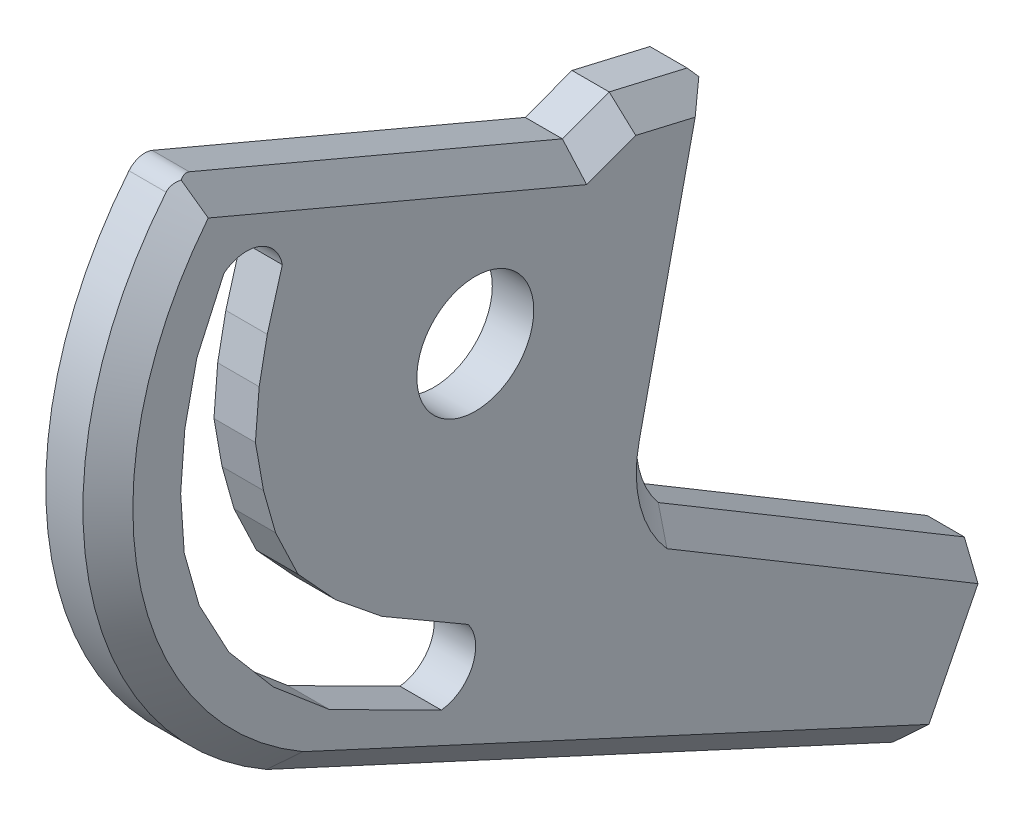
SolidWorks part; units mm, degrees
ref_plane "Front Plane" through (0, 0, 0) normal (0, 0, 1) x (1, 0, 0)
ref_plane "Top Plane" through (0, 0, 0) normal (0, 1, 0) x (1, 0, 0)
ref_plane "Right Plane" through (0, 0, 0) normal (1, 0, 0) x (0, 0, -1)
sketch "Sketch1" plane through (0, 0, 0) normal (1, 0, 0) x (0, 0, -1)
  line L0 (-32.2773, 373.0147) -> (-176.4769, 434.088)
  line L1 (-32.2773, 373.0147) -> (-14.1923, 379.6838)
  line L2 (-14.1923, 379.6838) -> (15.937, 372.6279)
  line L3 (15.937, 372.6279) -> (20.004, 367.4463)
  line L4 (4.7876, 232.7412) -> (123.0757, 162.0886)
  line L5 (123.0757, 162.0886) -> (95.4308, 107.1979)
  line L6 (95.4308, 107.1979) -> (-146.6474, 219.1027)
  line L7 (20.004, 367.4463) -> (-2.8283, 264.4678)
  arc A0 (-176.4769, 434.088) -> (-185.4304, 431.7266) centre (-179.3195, 426.7114) ccw
  arc A1 (-2.8283, 264.4678) -> (4.7876, 232.7412) centre (33.5047, 256.4121) ccw
  arc A2 (-185.4304, 431.7266) -> (-146.6474, 219.1027) centre (-75.9203, 341.8524) ccw
  point P15 (-206.502, 286.9138)
extrude "Boss-Extrude1" add sketch "Sketch1" along normal blind 16.0292
sketch "Sketch3" plane through (0, 0, 0) normal (1, 0, 0) x (0, 0, -1)
  line L8 (-78.2919, 238.2959) -> (-111.6505, 257.6792)
  line L9 (-111.6505, 257.6792) -> (-129.5034, 272.1379)
  line L10 (-129.5034, 272.1379) -> (-144.0934, 288.0154)
  line L11 (-144.0934, 288.0154) -> (-152.7635, 306.2173)
  line L12 (-150.1534, 394.6406) -> (-155.9692, 374.2553)
  line L13 (-155.9692, 374.2553) -> (-159.1107, 358.284)
  line L14 (-159.1107, 358.284) -> (-160.5603, 340.3603)
  line L15 (-160.5603, 340.3603) -> (-157.418, 322.6664)
  line L16 (-157.418, 322.6664) -> (-152.7635, 306.2173)
  line L17 (-88.7059, 214.8383) -> (-131.9141, 236.614)
  line L18 (-131.9141, 236.614) -> (-153.6977, 255.111)
  line L19 (-153.6977, 255.111) -> (-170.8186, 275.2926)
  line L20 (-170.8186, 275.2926) -> (-182.3268, 296.7429)
  line L21 (-182.3268, 296.7429) -> (-188.0723, 317.0301)
  line L22 (-188.0723, 317.0301) -> (-189.453, 337.7014)
  line L23 (-189.453, 337.7014) -> (-187.8531, 358.4545)
  line L24 (-187.8531, 358.4545) -> (-183.2089, 379.9098)
  line L25 (-183.2089, 379.9098) -> (-172.7454, 403.0434)
  arc A5 (-172.7454, 403.0434) -> (-150.1534, 394.6406) centre (-163.998, 391.9896) cw
  arc A6 (-78.2919, 238.2959) -> (-88.7059, 214.8383) centre (-90.2379, 229.5589) cw
  circle A7 centre (-75.5764, 330.8703) radius 22.5958
  circle A8 centre (-75.5764, 330.8703) radius 95.2308 construction
  circle A9 centre (-142.8532, 263.4704) radius 13.3731 construction
  point P17 (-144.0934, 288.0154)
  point P20 (-129.5034, 272.1379)
  point P24 (-182.3268, 296.7429)
  point P25 (-152.7635, 306.2173)
  point P28 (-142.8532, 263.4704)
  point P32 (-111.6505, 257.6792)
  point P35 (-157.418, 322.6664)
  point P38 (-160.5603, 340.3603)
  point P39 (-159.1107, 358.284)
  point P40 (-155.9692, 374.2553)
  point P43 (-158.9644, 405.1564)
  point P46 (-183.2089, 379.9098)
  point P47 (-187.8531, 358.4545)
  point P48 (-189.453, 337.7014)
  point P49 (-188.0723, 317.0301)
  point P50 (-170.8186, 275.2926)
  point P51 (-153.6977, 255.111)
  point P52 (-131.9141, 236.614)
  point P55 (-76.4347, 224.219)
  dimension "D39" = 45.1917
  dimension "D42" = 26.7462
extrude "Cut-Extrude1" cut sketch "Sketch3" along normal through all
sketch "Sketch4" plane through (0, 0, 0) normal (1, 0, 0) x (0, 0, -1)
  line L0 (-32.2773, 373.0147) -> (-176.4769, 434.088)
  line L1 (-32.2773, 373.0147) -> (-14.1923, 379.6838)
  line L2 (-14.1923, 379.6838) -> (15.937, 372.6279)
  line L3 (15.937, 372.6279) -> (20.004, 367.4463)
  line L4 (4.7876, 232.7412) -> (123.0757, 162.0886)
  line L5 (123.0757, 162.0886) -> (121.3007, 158.5642)
  line L6 (95.4308, 107.1979) -> (-146.6474, 219.1027)
  line L7 (20.004, 367.4463) -> (-2.8283, 264.4678)
  line L8 (-32.3775, 368.7827) -> (-177.9423, 430.4342)
  line L9 (93.6276, 112.3677) -> (-144.8343, 222.6007)
  line L10 (117.9128, 160.5877) -> (121.3007, 158.5642)
  line L11 (2.1992, 229.7026) -> (117.9128, 160.5877)
  line L12 (15.7584, 366.4807) -> (-6.671, 265.3198)
  line L13 (13.694, 369.1107) -> (15.7584, 366.4807)
  line L14 (-13.9392, 375.582) -> (13.694, 369.1107)
  line L15 (-32.3775, 368.7827) -> (-13.9392, 375.582)
  line L16 (117.9128, 160.5877) -> (93.6276, 112.3677) construction
  line L17 (93.6276, 112.3677) -> (97.2023, 110.7152)
  line L18 (97.2023, 110.7152) -> (95.4308, 107.1979)
  line L20 (123.0757, 162.0886) -> (95.4308, 107.1979) construction
  arc A0 (-176.4769, 434.088) -> (-185.4304, 431.7266) centre (-179.3195, 426.7114) ccw
  arc A1 (-2.8283, 264.4678) -> (4.7876, 232.7412) centre (33.5047, 256.4121) ccw
  arc A2 (-185.4304, 431.7266) -> (-146.6474, 219.1027) centre (-75.9203, 341.8524) ccw
  arc A3 (-177.9423, 430.4342) -> (-182.3879, 429.2296) centre (-179.3195, 426.7114) ccw
  arc A4 (-182.3879, 429.2296) -> (-144.8343, 222.6007) centre (-75.9203, 341.8524) ccw
  arc A5 (-6.671, 265.3198) -> (2.1992, 229.7026) centre (33.5047, 256.4121) ccw
  point P15 (-206.502, 286.9138)
  dimension "D1" = 3.936
extrude "Boss-Extrude2" add sketch "Sketch4" against normal blind 7.9779
chamfer "Chamfer4" distance 9.6464 2 edges at (16.0292, 163.1503, 25.6083) (16.0292, 316.4314, 215.2889)
chamfer "Chamfer5" distance 9.6464 6 edges at (16.0292, 197.4149, -63.9317) (16.0292, 247.7254, 2.6826) (16.0292, 315.9571, -8.5879) (16.0292, 376.1558, -0.8724) (16.0292, 376.3493, 23.2348) (16.0292, 402.6326, 102.2078)
move or copy body "Body-Move/Copy1" [suppressed] bodies to move or copy 103
